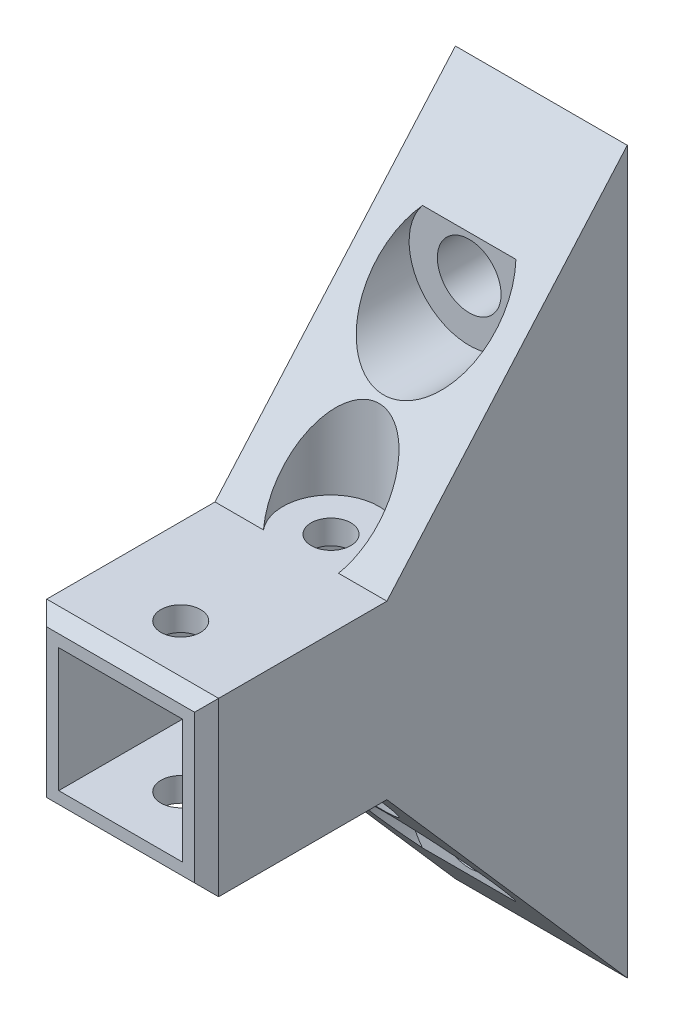
SolidWorks part; units mm, degrees
note: The reader was unsure of these and kept them because the rebuilt part matched: shared geometry of "草图3<4>", "草图3<5>", "草图4<3>".
material "ABS"
ref_plane "前视基准面" through (0, 0, 0) normal (0, 0, 1) x (1, 0, 0)
ref_plane "上视基准面" through (0, 0, 0) normal (0, 1, 0) x (1, 0, 0)
ref_plane "右视基准面" through (0, 0, 0) normal (1, 0, 0) x (0, 0, -1)
other "Configuration Table"
sketch "草图1" plane through (0, 0, 0) normal (0, 0, 1) x (1, 0, 0)
  line L0 (-5.15, 5.15) -> (5.15, 5.15)
  line L1 (-5, 5) -> (5, 5) construction
  line L2 (-5, 5) -> (-5, -5) construction
  line L3 (-5, -5) -> (5, -5) construction
  line L4 (5, 5) -> (5, -5) construction
  line L5 (0, -5) -> (0, 5) construction
  line L6 (-5, 0) -> (5, 0) construction
  line L7 (5.15, 5.15) -> (5.15, -5.15)
  line L8 (-5.15, -5.15) -> (5.15, -5.15)
  line L9 (-5.15, 5.15) -> (-5.15, -5.15)
  point P0 (0, 0)
  dimension "D1" = 10
  dimension "D2" = 0.15
extrude "拉伸-薄壁1" add sketch "草图1" along normal blind 35 thin thin type one direction wall 2
sketch "草图2" plane through (-7.15, 0, 0) normal (-1, 0, 0) x (0, 0, 1)
  line L0 (0, -30) -> (0, 30)
  line L1 (0, 30) -> (20, 7.15)
  line L2 (0, -30) -> (20, -7.15)
  line L4 (0, 7.15) -> (0, -7.15)
  line L5 (0, -7.15) -> (35, -7.15)
  line L6 (35, -7.15) -> (35, 7.15)
  line L7 (35, 7.15) -> (0, 7.15)
  line L8 (0, 7.15) -> (0, -7.15)
  line L9 (0, -7.15) -> (35, -7.15)
  line L10 (35, -7.15) -> (35, 7.15)
  line L11 (35, 7.15) -> (0, 7.15)
  point P7 (0, 0)
  point P9 (0, 0)
  point P12 (0, -30)
  line M6 (0, -7.15) -> (35, -7.15)
  line M8 (35, 7.15) -> (0, 7.15)
  dimension "D2" = 30
  dimension "D3" = 15
  dimension "D1" = 0
extrude "凸台-拉伸1" add sketch "草图2" against normal up to surface (14.3 mm away) contours L1 L0 M8 | L0 L2 M6 up to face at (7.15, 0, 17.5)
sketch "草图3" plane through (0, -7.15, 0) normal (0, -1, 0) x (1, 0, 0)
  circle A0 centre (0, 17.5) radius 1.65 construction
  circle A1 centre (0, 30) radius 1.65 construction
  circle A2 centre (0, 17.5) radius 1.65
  circle A3 centre (0, 30) radius 1.65
  circle A4 centre (0, 17.5) radius 4
  line M1 (-7.15, 20) -> (7.15, 20)
  dimension "D1" = 8
extrude "切除-拉伸1" cut sketch "草图3" against normal through all both and the other way through all contours A3 | A2
extrude "切除-拉伸2" cut sketch "草图3<4>" along normal through all contours A4 A2 M1 | A4 A2 M1
sketch "草图3<4>" plane through (0, -7.15, 0) normal (0, -1, 0) x (1, 0, 0) same geometry as "草图3"
extrude "切除-拉伸3" cut sketch "草图3<5>" against normal through all from surface at -14.3 contours A4 A2 M1 | A4 A2 M1 starting at face at (0, 7.15, 28.35)
sketch "草图3<5>" plane through (0, -7.15, 0) normal (0, -1, 0) x (1, 0, 0) same geometry as "草图3"
sketch "草图4" plane through (0, 0, 0) normal (0, 0, -1) x (-1, 0, 0)
  line L0 (0, 20) -> (0, -20)
  line L1 (7.865, 0) -> (-7.865, 0) construction
  circle A0 centre (0, 20) radius 2.65
  circle A1 centre (0, 20) radius 5
  circle A2 centre (0, -20) radius 2.65
  circle A3 centre (0, -20) radius 5
  point P4 (0, 0)
  point P11 (0, 0)
  dimension "D2" = 5.3
  dimension "D3" = 10
  dimension "D1" = 40
extrude "切除-拉伸4" cut sketch "草图4" against normal up to next
extrude "切除-拉伸5" cut sketch "草图4<3>" along normal offset from surface (8 mm away) 6 from offset 14
sketch "草图4<3>" plane through (0, 0, 0) normal (0, 0, -1) x (-1, 0, 0) same geometry as "草图4"
chamfer "倒角1" distance 1 angle 45 4 edges at (7.15, 0, 35) (0, 7.15, 35) (-7.15, 0, 35) (0, -7.15, 35)
